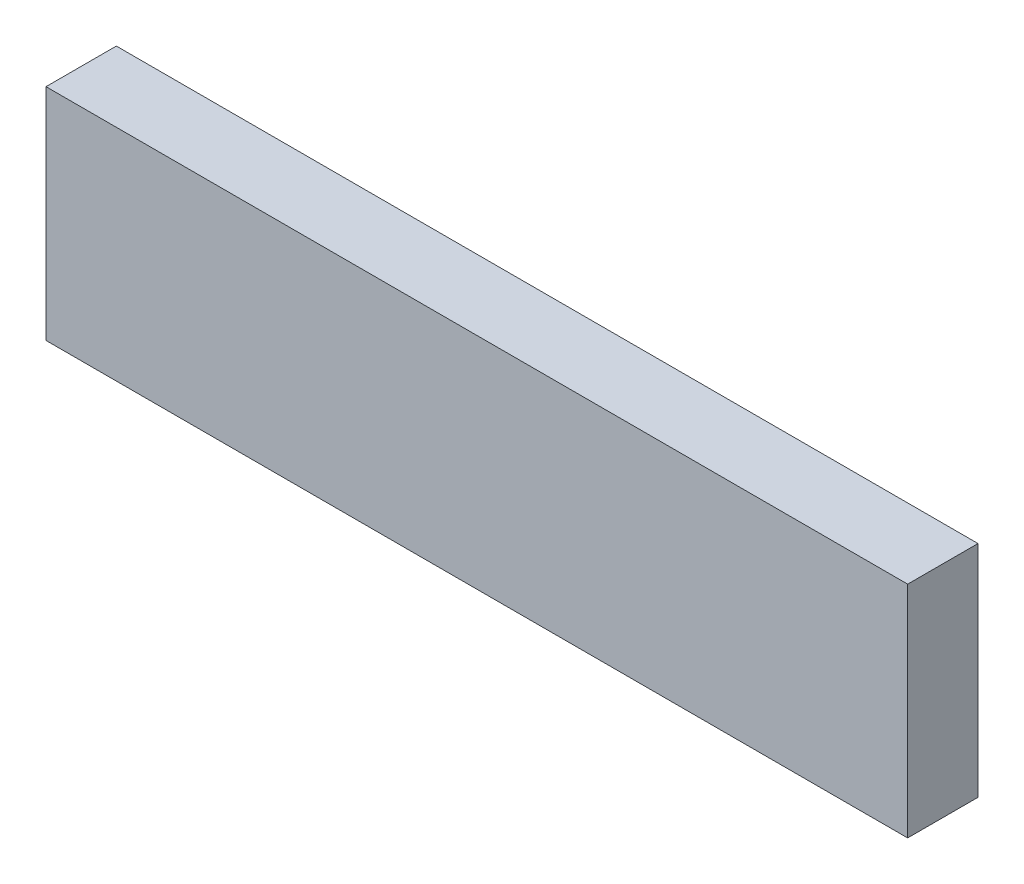
SolidWorks part; units mm, degrees
ref_plane "Front" through (0, 0, 0) normal (0, 0, 1) x (1, 0, 0)
ref_plane "Top" through (0, 0, 0) normal (0, 1, 0) x (1, 0, 0)
ref_plane "Right" through (0, 0, 0) normal (1, 0, 0) x (0, 0, -1)
sketch "Sketch1" plane through (0, 0, 0) normal (0, 1, 0) x (1, 0, 0)
  line L1 (-155.575, -12.7) -> (155.575, -12.7)
  line L2 (-155.575, -12.7) -> (-155.575, 12.7)
  line L3 (-155.575, 12.7) -> (155.575, 12.7)
  line L4 (155.575, -12.7) -> (155.575, 12.7)
  line L5 (-155.575, -12.7) -> (155.575, 12.7) construction
  line L6 (-155.575, 12.7) -> (155.575, -12.7) construction
  point P0 (0, 0)
  dimension "D1" = 311.15
  dimension "D2" = 25.4
extrude "Boss-Extrude1" add sketch "Sketch1" along normal mid plane 79.375
